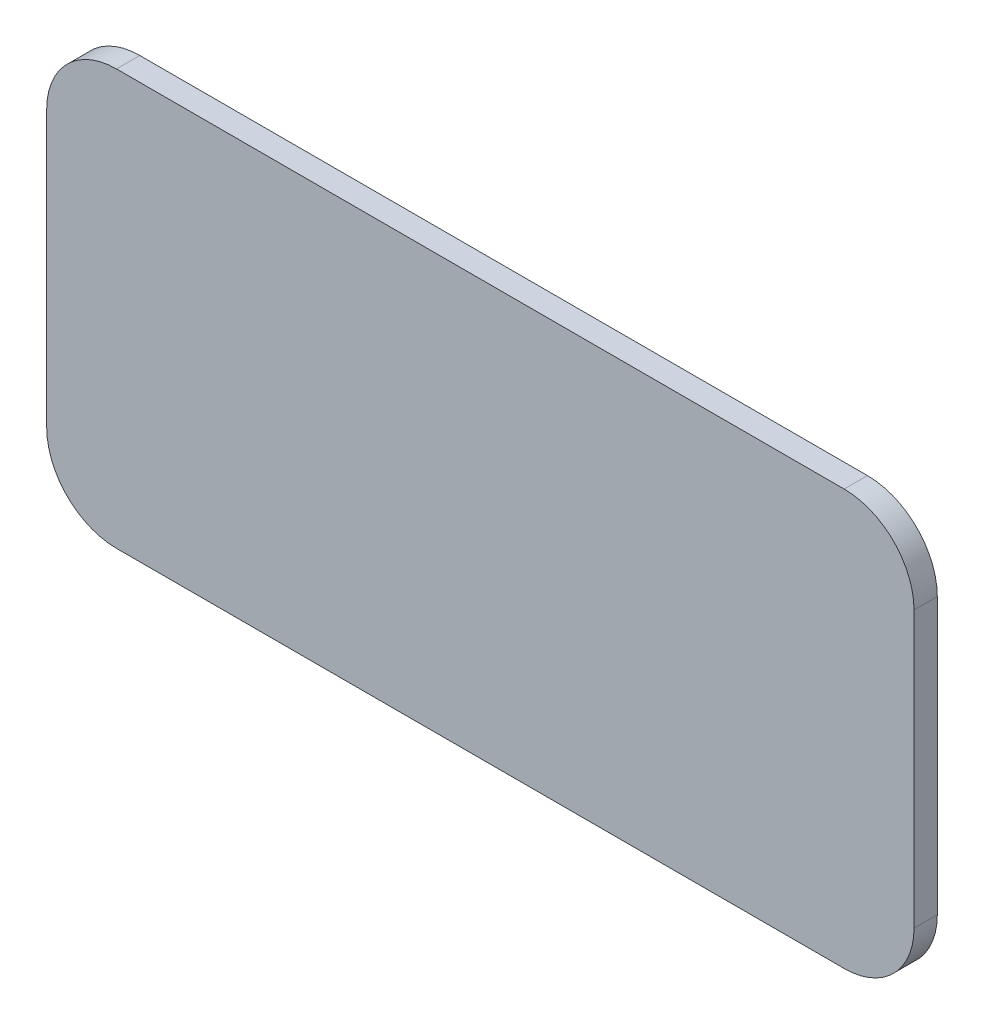
SolidWorks part; units mm, degrees
material "PC High Viscosity"
ref_plane "Front Plane" through (0, 0, 0) normal (0, 0, 1) x (1, 0, 0)
ref_plane "Top Plane" through (0, 0, 0) normal (0, 1, 0) x (1, 0, 0)
ref_plane "Right Plane" through (0, 0, 0) normal (1, 0, 0) x (0, 0, -1)
sketch "Sketch1" plane through (0, 0, 0) normal (0, 0, 1) x (1, 0, 0)
  line L3 (-62.9918, 96) -> (-250.5, 96)
  line L4 (-268.5, 78) -> (-268.5, 7)
  line L5 (-250.5, -11) -> (-62.9918, -11)
  line L13 (-44.9918, 7) -> (-44.9918, 78)
  arc A0 (-250.5, 96) -> (-268.5, 78) centre (-250.5, 78) ccw
  arc A1 (-268.5, 7) -> (-250.5, -11) centre (-250.5, 7) ccw
  arc A12 (-62.9918, -11) -> (-44.9918, 7) centre (-62.9918, 7) ccw
  arc A13 (-44.9918, 78) -> (-62.9918, 96) centre (-62.9918, 78) ccw
extrude "Boss-Extrude1" add sketch "Sketch1" along normal blind 6
